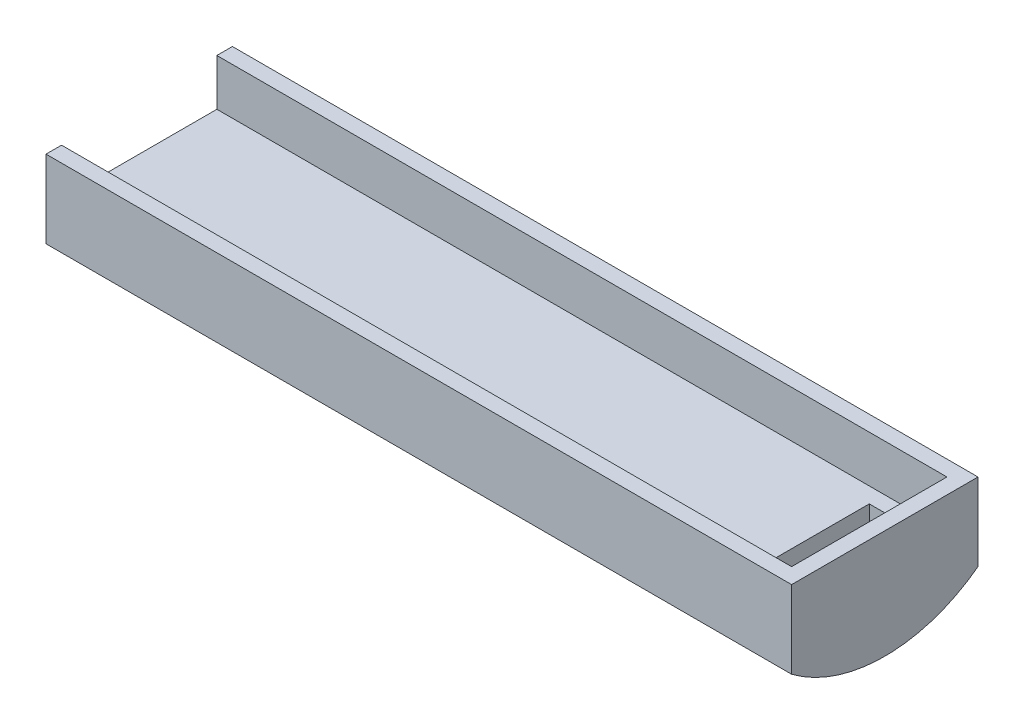
SolidWorks part; units mm, degrees
ref_plane "Front Plane" through (0, 0, 0) normal (0, 0, 1) x (1, 0, 0)
ref_plane "Top Plane" through (0, 0, 0) normal (0, 1, 0) x (1, 0, 0)
ref_plane "Right Plane" through (0, 0, 0) normal (1, 0, 0) x (0, 0, -1)
sketch "Sketch1" plane through (0, 0, 0) normal (0, 1, 0) x (1, 0, 0)
  line L1 (-152.4, -38.1) -> (152.4, -38.1)
  line L2 (-152.4, -38.1) -> (-152.4, 38.1)
  line L3 (-152.4, 38.1) -> (152.4, 38.1)
  line L4 (152.4, -38.1) -> (152.4, 38.1)
  line L5 (-152.4, -38.1) -> (152.4, 38.1) construction
  line L6 (-152.4, 38.1) -> (152.4, -38.1) construction
  point P0 (0, 0)
  dimension "D1" = 76.2
  dimension "D2" = 304.8
extrude "Boss-Extrude1" add sketch "Sketch1" against normal blind 6.35
sketch "Sketch3" plane through (0, 0, 0) normal (0, 1, 0) x (1, 0, 0)
  line L0 (152.4, -38.1) -> (152.4, 38.1) construction
  line L1 (120.65, -25.4) -> (146.05, -25.4)
  line L2 (120.65, -25.4) -> (120.65, 25.4)
  line L3 (120.65, 25.4) -> (146.05, 25.4)
  line L4 (146.05, -25.4) -> (146.05, 25.4)
  line L5 (120.65, -25.4) -> (146.05, 25.4) construction
  line L6 (120.65, 25.4) -> (146.05, -25.4) construction
  point P0 (133.35, 0)
  point P5 (0, 0)
  dimension "D1" = 25.4
  dimension "D2" = 50.8
  dimension "D3" = 6.35
extrude "Cut-Extrude2" cut sketch "Sketch3" against normal blind 25.4
sketch "Sketch4" plane through (0, 0, 0) normal (0, 1, 0) x (1, 0, 0)
  line L0 (152.4, -38.1) -> (152.4, 38.1) construction
  line L1 (-152.4, 38.1) -> (152.4, 38.1)
  line L2 (-152.4, 38.1) -> (-152.4, 31.75)
  line L3 (-152.4, 31.75) -> (152.4, 31.75)
  line L4 (152.4, 38.1) -> (152.4, 31.75)
  line L5 (146.05, -25.4) -> (146.05, 25.4) construction
  line L6 (-152.4, -38.1) -> (152.4, -38.1)
  line L7 (-152.4, -38.1) -> (-152.4, -31.75)
  line L8 (-152.4, -31.75) -> (152.4, -31.75)
  line L9 (152.4, -38.1) -> (152.4, -31.75)
  line L10 (152.4, 31.75) -> (146.05, 31.75)
  line L11 (152.4, 31.75) -> (152.4, -31.75)
  line L12 (152.4, -31.75) -> (146.05, -31.75)
  line L13 (146.05, 31.75) -> (146.05, -31.75)
  line M7 (146.05, 25.4) -> (146.05, -25.4)
  line M10 (152.4, -38.1) -> (152.4, 38.1)
  line M11 (152.4, 38.1) -> (-152.4, 38.1)
  line M12 (-152.4, 38.1) -> (-152.4, -38.1)
  line M13 (-152.4, -38.1) -> (152.4, -38.1)
  dimension "D1" = 6.35
  dimension "D2" = 6.35
extrude "Boss-Extrude2" add sketch "Sketch4" along normal blind 19.05 contours L3 M12 M10 M11 | L8 M12 M13 M10 | L3 L13 L8 M7 M10 region at (0, 0, -34.925) region at (149.225, 0, 0) region at (0, 0, 34.925)
sketch "Sketch5" plane through (-152.4, 0, 0) normal (-1, 0, 0) x (0, 0, 1)
  line L0 (-31.75, 19.05) -> (31.75, 19.05) construction
  line L1 (-38.1, -6.35) -> (-38.1, -12.7)
  line L2 (38.1, -6.35) -> (38.1, -12.7)
  line L3 (-38.1, -6.35) -> (38.1, -6.35)
  circle A0 centre (0, 38.1) radius 63.5
  line M5 (-38.1, -6.35) -> (38.1, -6.35)
  dimension "D1" = 127
  dimension "D2" = 19.05
extrude "Boss-Extrude3" add sketch "Sketch5" against normal up to surface (304.8 mm away) contours L1 A0 L2 M5 region at (-152.4, -14.3125, 0) up to face at (152.4, 6.35, 0)
